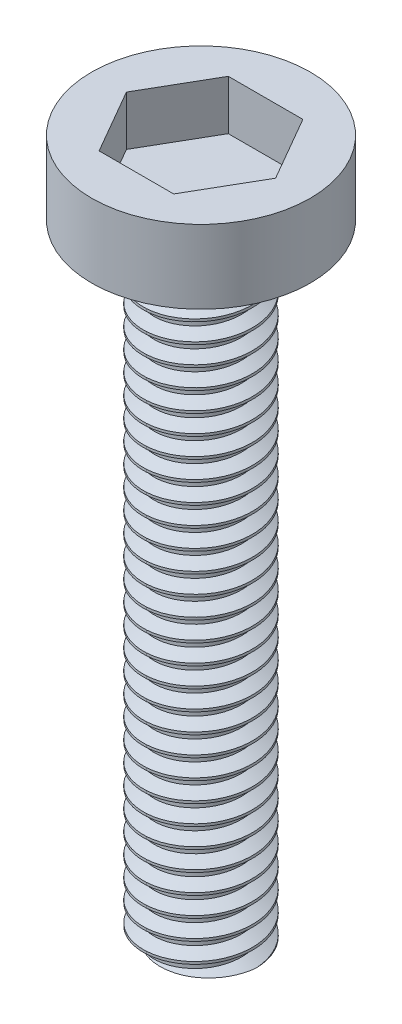
SolidWorks part; units mm, degrees
material "201 Acero inoxidable recocido (SS)"
ref_plane "Alzado" through (0, 0, 0) normal (0, 0, 1) x (1, 0, 0)
ref_plane "Planta" through (0, 0, 0) normal (0, 1, 0) x (1, 0, 0)
ref_plane "Vista lateral" through (0, 0, 0) normal (1, 0, 0) x (0, 0, -1)
sketch "Croquis1" plane through (0, 0, 0) normal (0, 1, 0) x (1, 0, 0)
  circle A0 centre (0, 0) radius 5.5
  dimension "D1" = 11
extrude "Saliente-Extruir1" add sketch "Croquis1" along normal blind 3.7
sketch "Croquis2" plane through (0, 0, 0) normal (0, 1, 0) x (1, 0, 0)
  circle A0 centre (0, 0) radius 2.75
  dimension "D1" = 5.5
extrude "Saliente-Extruir2" add sketch "Croquis2" against normal blind 31.23
ref_plane "Plano1" through (0, 3.7, 0) normal (0, 1, 0) x (1, 0, 0)
sketch "Croquis4" plane through (0, 3.7, 0) normal (0, 1, 0) x (1, 0, 0)
  line L1 (3.7528, 0) -> (1.8764, 3.25)
  line L2 (1.8764, 3.25) -> (-1.8764, 3.25)
  line L3 (-1.8764, 3.25) -> (-3.7528, 0)
  line L4 (-3.7528, 0) -> (-1.8764, -3.25)
  line L5 (-1.8764, -3.25) -> (1.8764, -3.25)
  line L6 (1.8764, -3.25) -> (3.7528, 0)
  circle A0 centre (0, 0) radius 3.25 construction
  dimension "D1" = 6.5
extrude "Cortar-Extruir1" cut sketch "Croquis4" against normal blind 2.5
thread "Rosca1" pitch 1 profile "Perfil de rosca1" start angle 1, offset 1, length 31.23, pitch 1, diameter 5.5
ref_plane "Plano2" through (2.7496, -32.23, -0.048) normal (0.0175, 0, 0.9998) x (0.9998, 0, -0.0175)
sketch "Perfil de rosca1" plane through (2.7496, -32.23, -0.048) normal (0.0175, 0, 0.9998) x (0.9998, 0, -0.0175)
  line L0 (0, 0) -> (0, 1) construction
  line L11 (0, 0) -> (0, 0.875)
  line L12 (0, 0.875) -> (-0.5413, 0.5625)
  line L13 (-0.5413, 0.5625) -> (-0.5413, 0.3125)
  line L15 (-0.5413, 0.3125) -> (0, 0)
  line L17 (-0.5413, 0.4375) -> (0, 0.4375) construction
  point P2 (0, 0)
  dimension "Pitch" = 1
  dimension "Profile_Angle" = 60
  dimension "Profile_Land" = 0.25
  dimension "Profile_Height" = 0.5413
